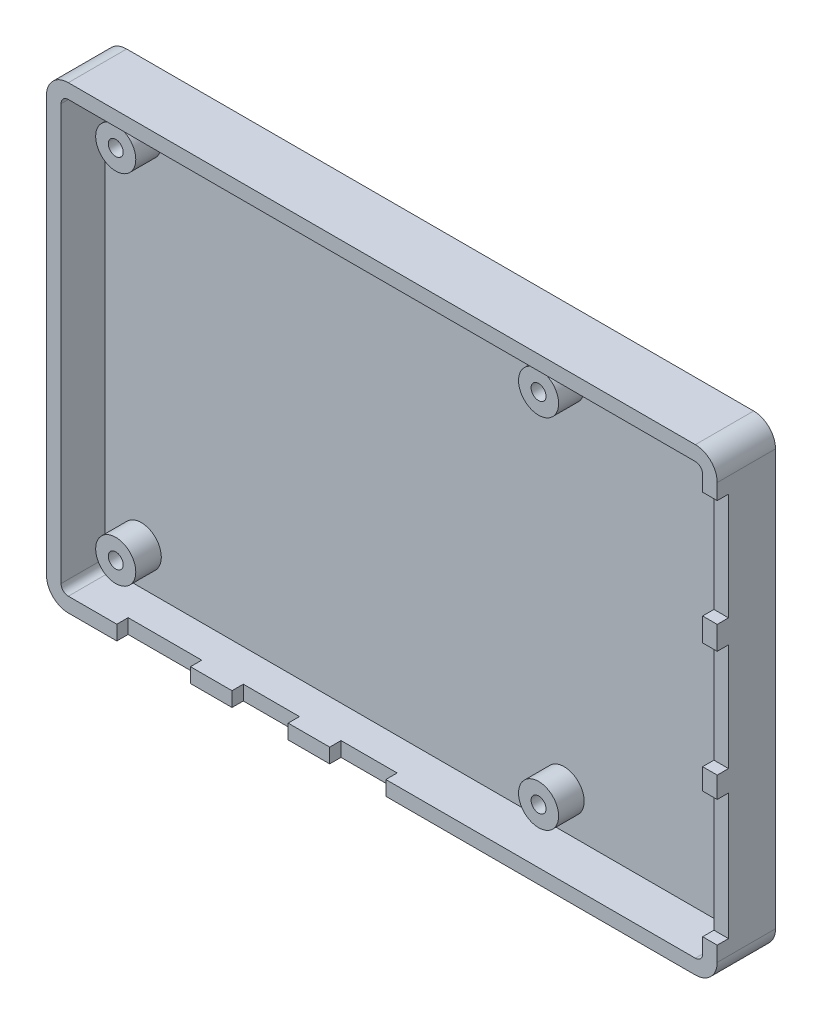
SolidWorks part; units mm, degrees
ref_plane "前视基准面" through (0, 0, 0) normal (0, 0, 1) x (1, 0, 0)
ref_plane "上视基准面" through (0, 0, 0) normal (0, 1, 0) x (1, 0, 0)
ref_plane "右视基准面" through (0, 0, 0) normal (1, 0, 0) x (0, 0, -1)
other "Configuration Table"
sketch "CaseEnvelope" plane through (0, 0, 0) normal (0, 0, 1) x (1, 0, 0)
  line L1 (-46, -31.5) -> (46, -31.5)
  line L2 (-46, -31.5) -> (-46, 31.5)
  line L3 (-46, 31.5) -> (46, 31.5)
  line L4 (46, -31.5) -> (46, 31.5)
  line L5 (-46, -31.5) -> (46, 31.5) construction
  line L6 (-46, 31.5) -> (46, -31.5) construction
  point P0 (0, 0)
  dimension "Length" = 92
  dimension "Width" = 63
extrude "Bottom_Envelope" add sketch "CaseEnvelope" along normal blind 8
fillet "Outside_R3" radius 3 4 edges at (46, 31.5, 4) (46, -31.5, 4) (-46, 31.5, 4) (-46, -31.5, 4) tangent propagation no
shell "抽壳1" thickness 2 removed face at (0, 0, 8)
sketch "SidePort_Profile_1" plane through (0, 0, 0) normal (0, 0, 1) x (1, 0, 0)
  line L0 (-36.35, -40) -> (-26.25, -40)
  line L1 (-26.25, -40) -> (-26.25, -27)
  line L2 (-26.25, -27) -> (-36.35, -27)
  line L3 (-36.35, -27) -> (-36.35, -40)
extrude "SidePort_Clearance_1" cut sketch "SidePort_Profile_1" along normal blind 4.5 from offset 6.45
sketch "SidePort_Profile_2" plane through (0, 0, 0) normal (0, 0, 1) x (1, 0, 0)
  line L0 (-20.55, -40) -> (-12.85, -40)
  line L1 (-12.85, -40) -> (-12.85, -27)
  line L2 (-12.85, -27) -> (-20.55, -27)
  line L3 (-20.55, -27) -> (-20.55, -40)
extrude "SidePort_Clearance_2" cut sketch "SidePort_Profile_2" along normal blind 4.7 from offset 6.45
sketch "SidePort_Profile_3" plane through (0, 0, 0) normal (0, 0, 1) x (1, 0, 0)
  line L0 (-7.15, -40) -> (0.55, -40)
  line L1 (0.55, -40) -> (0.55, -27)
  line L2 (0.55, -27) -> (-7.15, -27)
  line L3 (-7.15, -27) -> (-7.15, -40)
extrude "SidePort_Clearance_3" cut sketch "SidePort_Profile_3" along normal blind 4.7 from offset 6.45
sketch "EndPort_Profile_1" plane through (0, 0, 0) normal (0, 0, 1) x (1, 0, 0)
  line L0 (42, -26.45) -> (53, -26.45)
  line L1 (53, -26.45) -> (53, -9.15)
  line L2 (53, -9.15) -> (42, -9.15)
  line L3 (42, -9.15) -> (42, -26.45)
extrude "EndPort_Clearance_1" cut sketch "EndPort_Profile_1" along normal blind 14.6 from offset 6.45
sketch "EndPort_Profile_2" plane through (0, 0, 0) normal (0, 0, 1) x (1, 0, 0)
  line L0 (42, -6.25) -> (53, -6.25)
  line L1 (53, -6.25) -> (53, 8.45)
  line L2 (53, 8.45) -> (42, 8.45)
  line L3 (42, 8.45) -> (42, -6.25)
extrude "EndPort_Clearance_2" cut sketch "EndPort_Profile_2" along normal blind 16.3 from offset 6.45
sketch "EndPort_Profile_3" plane through (0, 0, 0) normal (0, 0, 1) x (1, 0, 0)
  line L0 (42, 11.65) -> (53, 11.65)
  line L1 (53, 11.65) -> (53, 26.35)
  line L2 (53, 26.35) -> (42, 26.35)
  line L3 (42, 26.35) -> (42, 11.65)
extrude "EndPort_Clearance_3" cut sketch "EndPort_Profile_3" along normal blind 16.3 from offset 6.45
sketch "Standoff_Rings" plane through (0, 0, 0) normal (0, 0, 1) x (1, 0, 0)
  circle A0 centre (-39, -24.5) radius 2.75
  circle A1 centre (-39, 24.5) radius 2.75
  circle A2 centre (19, -24.5) radius 2.75
  circle A3 centre (19, 24.5) radius 2.75
  circle A4 centre (-39, -24.5) radius 1.025
  circle A5 centre (-39, 24.5) radius 1.025
  circle A6 centre (19, -24.5) radius 1.025
  circle A7 centre (19, 24.5) radius 1.025
extrude "Four_M2p5_Standoffs_2p05_Pilot" add sketch "Standoff_Rings" along normal blind 3.5 from offset 2
